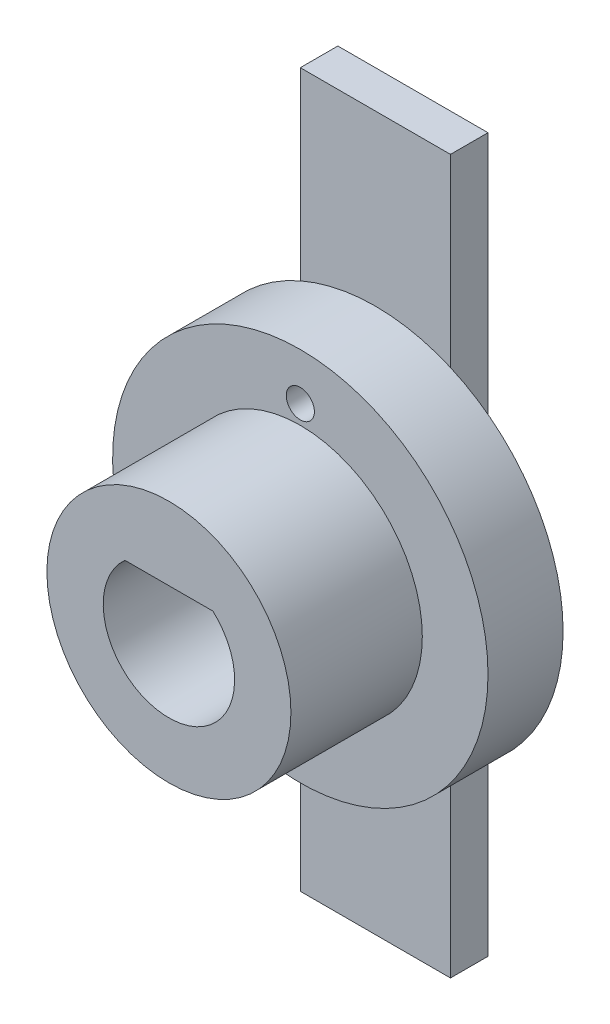
SolidWorks part; units mm, degrees
ref_plane "Plan de face" through (0, 0, 0) normal (0, 0, 1) x (1, 0, 0)
ref_plane "Plan de dessus" through (0, 0, 0) normal (0, 1, 0) x (1, 0, 0)
ref_plane "Plan de droite" through (0, 0, 0) normal (1, 0, 0) x (0, 0, -1)
sketch "Esquisse1" plane through (0, 0, 0) normal (0, 0, 1) x (1, 0, 0)
  line L8 (0, -7.5) -> (0, 7.5) construction
  circle A2 centre (0, -7.5) radius 0.75
  circle A3 centre (0, 7.5) radius 0.75
  circle A4 centre (0, 0) radius 10
  point P6 (0, 0)
  dimension "D2" = 1.5
  dimension "D3" = 1.5
  dimension "D4" = 20
  dimension "D1" = 15
extrude "Boss.-Extru.1" add sketch "Esquisse1" along normal blind 4
sketch "Esquisse2" [suppressed] plane through (0, 0, 10) normal (0, 0, 1) x (1, 0, 0)
  line L0 (-2.2, -2.0396) -> (-2.2, 2.0396)
  line L1 (3, -1.1913) -> (3, 1.3119) construction
  arc A0 (-2.2, -2.0396) -> (-2.2, 2.0396) centre (0, 0) ccw
  dimension "D1" = 6
  dimension "D2" = 5.2
extrude "Enlèv. mat.-Extru.1" [suppressed] cut sketch "Esquisse2" against normal offset from surface (8 mm away) 2 up to face at (10, 0, 0)
sketch "Esquisse3" plane through (0, 0, 4) normal (0, 0, 1) x (1, 0, 0)
  line L0 (-2.3431, 2.6) -> (2.3431, 2.6)
  line L1 (-0.8426, -3.5) -> (1.2459, -3.5) construction
  circle A0 centre (0, 0) radius 6.5
  arc A1 (-2.3431, 2.6) -> (2.3431, 2.6) centre (0, 0) ccw
  dimension "D1" = 7
  dimension "D3" = 13
  dimension "D2" = 6.1
extrude "Boss.-Extru.2" add sketch "Esquisse3" along normal blind 7
sketch "Esquisse4" plane through (0, 0, 0) normal (0, 0, -1) x (-1, 0, 0)
  line L1 (-4, 19) -> (4, 19)
  line L2 (-4, 19) -> (-4, -19)
  line L3 (-4, -19) -> (4, -19)
  line L4 (4, 19) -> (4, -19)
  point P4 (0, 19)
  point P5 (-4, 0)
  dimension "D1" = 8
  dimension "D2" = 38
extrude "Boss.-Extru.3" add sketch "Esquisse4" along normal blind 2
